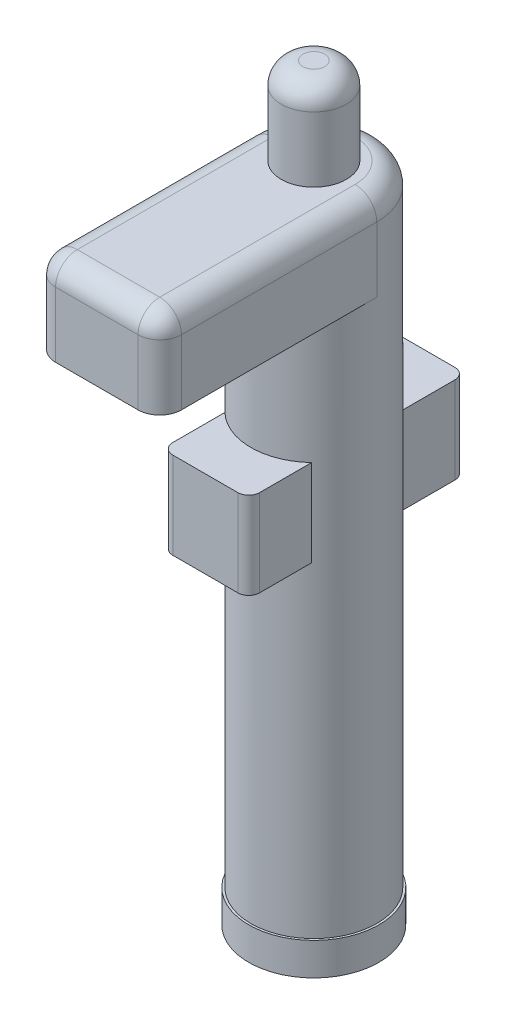
SolidWorks part; units mm, degrees
ref_plane "Front Plane" through (0, 0, 0) normal (0, 0, 1) x (1, 0, 0)
ref_plane "Top Plane" through (0, 0, 0) normal (0, 1, 0) x (1, 0, 0)
ref_plane "Right Plane" through (0, 0, 0) normal (1, 0, 0) x (0, 0, -1)
sketch "Sketch2" plane through (0, 0, 0) normal (0, 1, 0) x (1, 0, 0)
  circle A0 centre (0, 0) radius 2.9
  dimension "D1" = 5.8
extrude "Boss-Extrude1" add sketch "Sketch2" along normal blind 25
sketch "Sketch4" plane through (0, 25, 0) normal (0, 1, 0) x (1, 0, 0)
  line L2 (-2.9, 0) -> (-2.9, -10)
  line L3 (-2.9, -10) -> (2.9, -10)
  line L4 (2.9, 0) -> (2.9, -10)
  circle A2 centre (0, 0) radius 2.9 construction
  arc A3 (-2.9, 0) -> (2.9, 0) centre (0, 0) ccw
  point P0 (0, 0)
  dimension "D1" = 10
  dimension "D2" = 5.8
  dimension "D3" = 10
extrude "Boss-Extrude2" add sketch "Sketch4" along normal blind 4 separate body
sketch "Sketch5" plane through (0, 25, 0) normal (0, 1, 0) x (1, 0, 0)
  circle A0 centre (0, 0) radius 2.9 construction
  circle A1 centre (0, 0) radius 2.9
extrude "Boss-Extrude3" add sketch "Sketch5" along normal blind 4
fillet "Fillet1" radius 1 6 edges at (0, 29, -2.9) (2.9, 29, 5) (-2.9, 29, 5) (-2.9, 27, 10) (2.9, 27, 10) (0, 29, 10)
sketch "Sketch6" plane through (0, 0, 0) normal (0, 0, 1) x (1, 0, 0)
  line L0 (-2.9, 0) -> (2.9, 0) construction
  line L1 (-2.9, 0) -> (2.9, 0) construction
  line L2 (-2.9, 25) -> (2.9, 25) construction
  line L3 (-2.9, 25) -> (2.9, 25) construction
  line L4 (0, 25) -> (0, 17) construction
  line L6 (2, 19) -> (-2, 19)
  line L7 (2, 19) -> (2, 15)
  line L8 (2, 15) -> (-2, 15)
  line L9 (-2, 19) -> (-2, 15)
  line L10 (2, 19) -> (-2, 15) construction
  line L11 (2, 15) -> (-2, 19) construction
  circle A0 centre (0, 17) radius 2 construction
  dimension "D2" = 4
  dimension "D1" = 8
  dimension "D3" = 4
  dimension "D4" = 4
extrude "Boss-Extrude6" add sketch "Sketch6" along normal blind 5 and the other way blind 5
fillet "Fillet3" radius 0.5 4 edges at (-2, 17, -5) (2, 17, -5) (2, 17, 5) (-2, 17, 5)
sketch "Sketch7" plane through (0, 29, 0) normal (0, 1, 0) x (1, 0, 0)
  circle A0 centre (0, 0) radius 1.5
  dimension "D1" = 3
extrude "Boss-Extrude4" add sketch "Sketch7" along normal blind 4 contours A0
fillet "Fillet2" radius 1 1 edges at (0, 33, 1.5)
sketch "Sketch8" plane through (0, 0, 0) normal (0, -1, 0) x (-1, 0, 0)
  circle A0 centre (0, 0) radius 3
  dimension "D1" = 6
extrude "Boss-Extrude5" add sketch "Sketch8" along normal blind 1.5
